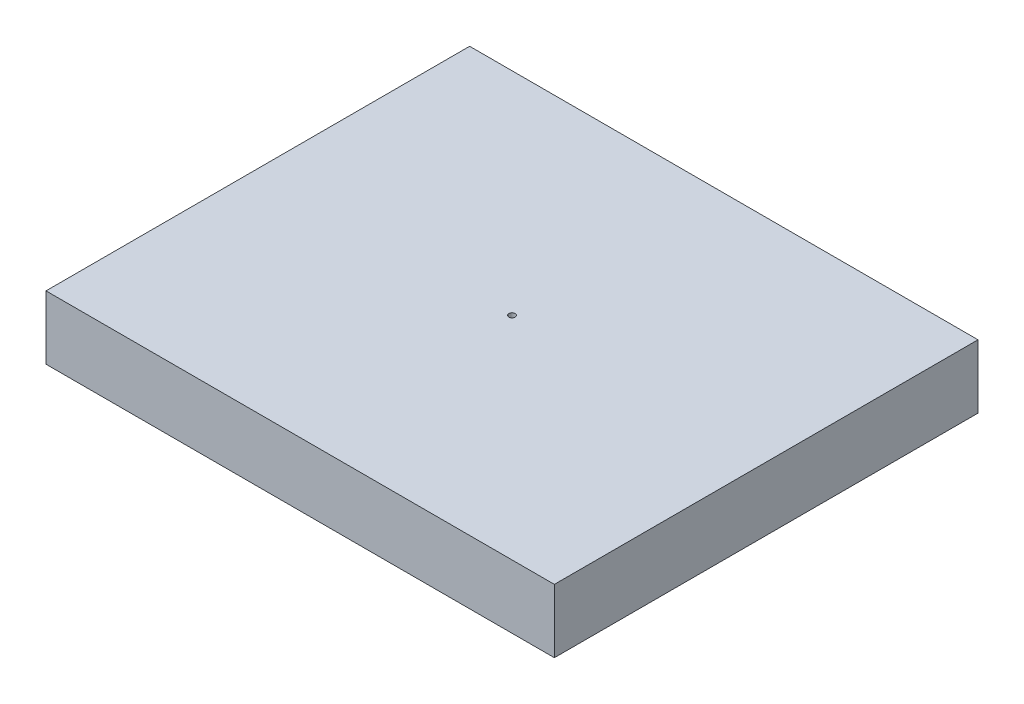
SolidWorks part; units mm, degrees
ref_plane "Front Plane" through (0, 0, 0) normal (0, 0, 1) x (1, 0, 0)
ref_plane "Top Plane" through (0, 0, 0) normal (0, 1, 0) x (1, 0, 0)
ref_plane "Right Plane" through (0, 0, 0) normal (1, 0, 0) x (0, 0, -1)
sketch "Sketch1" plane through (0, 0, 0) normal (0, 1, 0) x (1, 0, 0)
  line L1 (-120, -100) -> (120, -100)
  line L2 (-120, -100) -> (-120, 100)
  line L3 (-120, 100) -> (120, 100)
  line L4 (120, -100) -> (120, 100)
  line L5 (-120, -100) -> (120, 100) construction
  line L6 (-120, 100) -> (120, -100) construction
  point P0 (0, 0)
  dimension "D1" = 240
  dimension "D2" = 200
extrude "Boss-Extrude1" add sketch "Sketch1" along normal mid plane 30
sketch "Sketch2" plane through (0, 15, 0) normal (0, 1, 0) x (1, 0, 0)
  circle A0 centre (0, 0) radius 1.5
  dimension "D1" = 3
extrude "Cut-Extrude1" cut sketch "Sketch2" against normal through all
